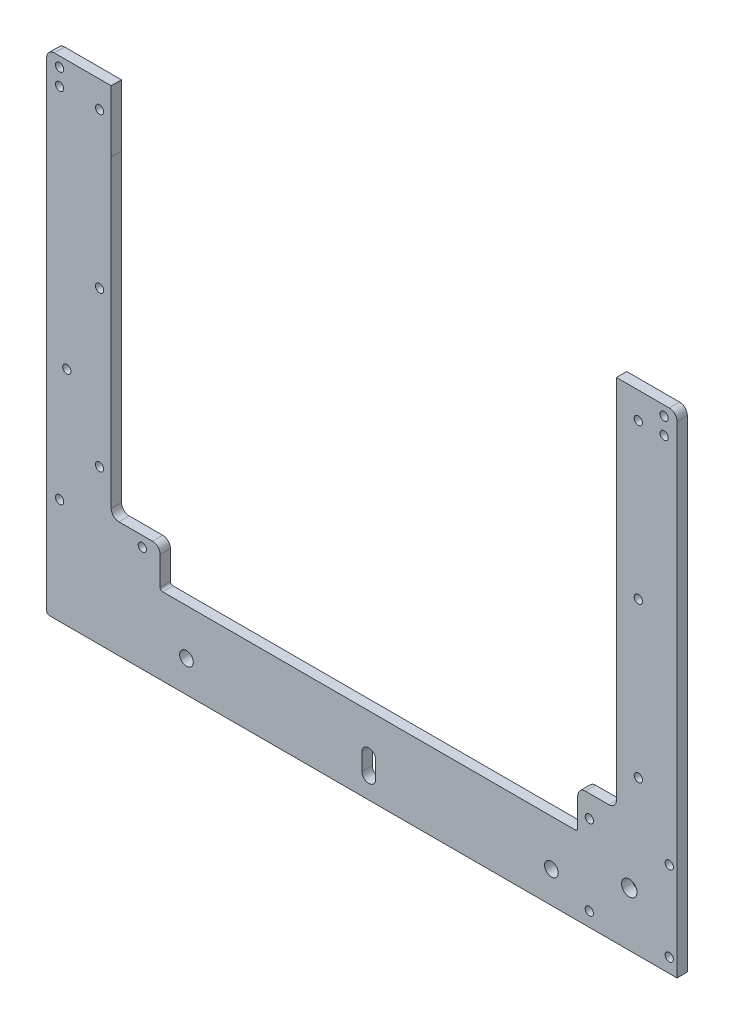
SolidWorks part; units mm, degrees
ref_plane "Plano frontal" through (0, 0, 0) normal (0, 0, 1) x (1, 0, 0)
ref_plane "Plano superior" through (0, 0, 0) normal (0, 1, 0) x (1, 0, 0)
ref_plane "Plano direito" through (0, 0, 0) normal (1, 0, 0) x (0, 0, -1)
sketch "Esboço1" plane through (0, 0, 0) normal (0, 0, 1) x (1, 0, 0)
  line L0 (-36.7564, -93.1156) -> (-55.7564, -93.1156)
  line L1 (-35.7564, -108.1156) -> (124.2436, -108.1156)
  line L2 (-55.7564, -79.1156) -> (-55.7564, 27.8844)
  line L3 (-52.7564, 30.8844) -> (141.2436, 30.8844)
  line L4 (144.2436, -79.1156) -> (144.2436, 27.8844)
  line L5 (168.2436, -138.1156) -> (-79.7564, -138.1156)
  line L6 (169.2436, -137.1156) -> (169.2436, 48.8844)
  line L7 (166.2436, 51.8844) -> (-77.7564, 51.8844)
  line L8 (-80.7564, -137.1156) -> (-80.7564, 48.8844)
  line L9 (44.2436, -142.1156) -> (44.2436, -132.526) construction
  line L10 (144.2436, -93.1156) -> (144.2436, -79.1156)
  line L11 (-36.7564, -93.1156) -> (-36.7564, -107.1156)
  line L12 (125.2436, -93.1156) -> (144.2436, -93.1156)
  line L13 (-36.7564, -93.1156) -> (-41.6564, -93.1156) construction
  line L15 (125.2436, -93.1156) -> (125.2436, -107.1156)
  line L17 (-55.7564, -93.1156) -> (-55.7564, -79.1156)
  arc A2 (141.2436, 30.8844) -> (144.2436, 27.8844) centre (141.2436, 27.8844) cw
  arc A3 (-55.7564, 27.8844) -> (-52.7564, 30.8844) centre (-52.7564, 27.8844) cw
  arc A4 (-77.7564, 51.8844) -> (-80.7564, 48.8844) centre (-77.7564, 48.8844) ccw
  arc A5 (169.2436, 48.8844) -> (166.2436, 51.8844) centre (166.2436, 48.8844) ccw
  arc A6 (-36.7564, -107.1156) -> (-35.7564, -108.1156) centre (-35.7564, -107.1156) ccw
  arc A7 (-79.7564, -138.1156) -> (-80.7564, -137.1156) centre (-79.7564, -137.1156) cw
  arc A9 (168.2436, -138.1156) -> (169.2436, -137.1156) centre (168.2436, -137.1156) ccw
  arc A12 (125.2436, -107.1156) -> (124.2436, -108.1156) centre (124.2436, -107.1156) cw
  dimension "D2" = 1
  dimension "D10" = 44
  dimension "D11" = 3
  dimension "D12" = 45
  dimension "D13" = 1
  dimension "D3" = 250
  dimension "D4" = 190
  dimension "D5" = 21
  dimension "D6" = 30
  dimension "D7" = 25
  dimension "D8" = 25
  dimension "D9" = 45
extrude "Ressalto-extrusão1" add sketch "Esboço1" along normal blind 4
fillet "Filete1" radius 3 4 edges at (144.2436, -93.1156, 2) (125.2436, -93.1156, 2) (-55.7564, -93.1156, 2) (-36.7564, -93.1156, 2)
hole_wizard "M3 Clearance Hole1" positions "Esboço11" profile "Esboço10" hole size "M3" standard "ISO" end condition through all
sketch "Esboço11" plane through (0, 0, 0) normal (0, 0, -1) x (-1, 0, 0)
  point P0 (-164.23, -97.103)
  point P12 (43.67, -97.103)
  point P15 (75.7428, -97.103)
sketch "Esboço10" plane through (164.23, -97.103, 0) normal (1, 0, 0) x (0, 1, 0)
  line L0 (0, 0) -> (0, 4)
  line L1 (0, 4) -> (1.6, 4)
  line L2 (1.6, 4) -> (1.6, 0)
  line L5 (1.6, 0) -> (0, 0)
  line L11 (0, -6.35) -> (0, 107.95) construction
  dimension "Thru Hole Dia." = 3.2
  dimension "Thru Hole Depth" = 4
sketch "Esboço16" plane through (0, 0, 4) normal (0, 0, 1) x (1, 0, 0)
  line L0 (150.0557, -138.1156) -> (169.2436, -138.1156) construction
  line L3 (-79.7564, -138.1156) -> (168.2436, -138.1156) construction
  line L5 (169.2436, -137.1156) -> (169.2436, 48.8844) construction
  line L6 (169.2436, -127.14) -> (169.2436, -138.1156) construction
hole_wizard "Furo com folga de M32" positions "Esboço19" profile "Esboço18" hole size "M3" standard "Ansi Metric" end condition through all
sketch "Esboço19" plane through (0, 0, 4) normal (0, 0, 1) x (1, 0, 0)
  point P14 (44.2436, 46.9871)
sketch "Esboço18" plane through (44.2436, 46.9871, 4) normal (1, 0, 0) x (0, -1, 0)
  line L0 (0, 0) -> (0, 4)
  line L1 (0, 4) -> (1.435, 4)
  line L2 (1.435, 4) -> (1.435, 0)
  line L5 (1.435, 0) -> (0, 0)
  line L11 (0, -6.35) -> (0, 107.95) construction
  dimension "Thru Hole Dia." = 2.87
  dimension "Thru Hole Depth" = 4
hole_wizard "M3 Clearance Hole2" positions "Sketch2" profile "Sketch1" hole size "M3" standard "ISO" end condition through all
sketch "Sketch2" plane through (0, 0, 4) normal (0, 0, 1) x (1, 0, 0)
  point P0 (161.5603, 35.4802)
  point P3 (161.5603, 4.4802)
sketch "Sketch1" plane through (161.5603, 35.4802, 4) normal (1, 0, 0) x (0, -1, 0)
  line L0 (0, 0) -> (0, 4)
  line L1 (0, 4) -> (1.6, 4)
  line L2 (1.6, 4) -> (1.6, 0)
  line L5 (1.6, 0) -> (0, 0)
  line L11 (0, -6.35) -> (0, 107.95) construction
  dimension "Thru Hole Dia." = 3.2
  dimension "Thru Hole Depth" = 4
sketch "Sketch3" plane through (0, 0, 4) normal (0, 0, 1) x (1, 0, 0)
  line L3 (44.2436, 30.8844) -> (44.2436, 18.6097) construction
  line L8 (141.2436, 30.8844) -> (-52.7564, 30.8844) construction
  line L9 (183.6742, -138.1156) -> (156.2436, -138.1156)
  line L10 (183.6742, 51.8844) -> (183.6742, -138.1156)
  line L11 (156.2436, 51.8844) -> (183.6742, 51.8844)
  line L12 (156.2436, -138.1156) -> (156.2436, 51.8844)
extrude "Cut-Extrude1" cut sketch "Sketch3" against normal blind 10
sketch "Sketch5" plane through (0, 0, 0) normal (0, 0, -1) x (-1, 0, 0)
  line L0 (-44.2436, 30.8844) -> (-44.2436, 20.8984) construction
  line L1 (-141.2436, 30.8844) -> (52.7564, 30.8844) construction
  line L2 (-145.2403, -97.5002) -> (-140.2436, -97.5002)
  line L3 (-145.2403, 30.8844) -> (-145.2403, -97.5002)
  line L4 (-141.2436, 30.8844) -> (52.7564, 30.8844) construction
  line L6 (-137.2442, 30.8844) -> (-145.2403, 30.8844)
  line L10 (-140.2436, 27.9415) -> (-140.2436, -97.5002)
  arc A0 (-137.2442, 30.8844) -> (-140.2436, 27.9415) centre (-137.2442, 27.8844) ccw
  dimension "D1" = 3
extrude "Boss-Extrude1" add sketch "Sketch5" against normal blind 4
fillet "Fillet3" radius 3 1 edges at (156.2436, 51.8844, 2)
sketch "Sketch10" plane through (0, 0, 0) normal (0, 0, -1) x (-1, 0, 0)
  line L0 (-156.2436, -138.1156) -> (-156.2436, 48.8844)
  line L1 (-156.2436, -138.1156) -> (-163.7436, -138.1156)
  line L4 (-150.0557, -138.1156) -> (-169.2436, -138.1156) construction
  line L6 (-163.7436, -138.1156) -> (-163.7436, 51.8844)
  line L10 (-163.7436, 51.8844) -> (-153.2436, 51.8844)
  arc A1 (-153.2436, 51.8844) -> (-156.2436, 48.8844) centre (-153.2436, 48.8844) ccw
extrude "Boss-Extrude3" add sketch "Sketch10" against normal blind 4
hole_wizard "M3 Clearance Hole4" positions "Sketch12" profile "Sketch11" hole size "M3" standard "ISO" end condition through all
sketch "Sketch12" plane through (0, 0, 0) normal (0, 0, -1) x (-1, 0, 0)
  point P0 (-160.7436, -101.6156)
  point P2 (-160.7436, -132.6156)
  point P5 (-129.7436, -132.6156)
  point P6 (-129.7436, -101.6156)
sketch "Sketch11" plane through (160.7436, -101.6156, 0) normal (1, 0, 0) x (0, 1, 0)
  line L0 (0, 0) -> (0, 4)
  line L1 (0, 4) -> (1.6, 4)
  line L2 (1.6, 4) -> (1.6, 0)
  line L5 (1.6, 0) -> (0, 0)
  line L11 (0, -6.35) -> (0, 107.95) construction
  dimension "Thru Hole Dia." = 3.2
  dimension "Thru Hole Depth" = 4
fillet "Fillet5" radius 3 2 edges at (163.7436, 51.8844, 2) (140.2436, -93.1156, 2)
hole_wizard "M5 Clearance Hole1" positions "Esboço15" profile "Esboço14" hole size "M5" standard "ISO" end condition through all
sketch "Esboço15" plane through (0, 0, 0) normal (0, 0, -1) x (-1, 0, 0)
  point P1 (-115.0336, -125.8856)
  point P3 (26.5464, -125.8856)
  point P4 (-44.1899, -129.8656)
sketch "Esboço14" plane through (115.0336, -125.8856, 0) normal (1, 0, 0) x (0, 1, 0)
  line L0 (0, 0) -> (0, 4)
  line L1 (0, 4) -> (2.65, 4)
  line L2 (2.65, 4) -> (2.65, 0)
  line L5 (2.65, 0) -> (0, 0)
  line L11 (0, -6.35) -> (0, 107.95) construction
  dimension "Thru Hole Dia." = 5.3
  dimension "Thru Hole Depth" = 4
sketch "Sketch15" plane through (0, 0, 0) normal (0, 0, -1) x (-1, 0, 0)
  circle A1 centre (-145.2436, -117.1156) radius 3
  point P0 (-145.2436, -117.1156)
  point P2 (-144.7712, -129.7569)
  point P4 (-145.2436, -117.1156)
  point P5 (-144.7712, -129.7569)
  dimension "D1" = 6
extrude "Cut-Extrude6" cut sketch "Sketch15" against normal through all
sketch "Sketch17" plane through (0, 0, 0) normal (0, 0, -1) x (-1, 0, 0)
  line L1 (-140.2436, 27.9415) -> (55.7564, 27.9415)
  line L2 (-140.2436, 27.9415) -> (-140.2436, 51.8844)
  line L3 (-140.2436, 51.8844) -> (55.7564, 51.8844)
  line L4 (55.7564, 27.9415) -> (55.7564, 51.8844)
extrude "Cut-Extrude8" cut sketch "Sketch17" against normal blind 5
sketch "Sketch23" plane through (0, 0, 4) normal (0, 0, 1) x (1, 0, 0)
  line L0 (-55.7564, 27.8844) -> (-55.7564, -90.1156) construction
  line L1 (-55.7564, -56.9456) -> (-19.6598, -56.9456)
  line L2 (-55.7564, -56.9456) -> (-55.7564, -46.9456)
  line L3 (-55.7564, -46.9456) -> (-19.6598, -46.9456)
  line L5 (-18.4098, -51.9456) -> (-16.0426, -51.9456) construction
  line L6 (-19.6598, 45.5544) -> (-55.7564, 45.5544)
  line L8 (-19.6598, 35.5544) -> (-55.7564, 35.5544)
  line L9 (-55.7564, 45.5544) -> (-55.7564, 35.5544)
  arc A1 (-19.6598, -50.6956) -> (-19.6598, -53.1956) centre (-19.6598, -51.9456) ccw construction
  arc A2 (-19.6598, 35.5544) -> (-19.6598, 45.5544) centre (-19.6598, 40.5544) ccw
  arc A3 (-19.6598, -56.9456) -> (-19.6598, -46.9456) centre (-19.6598, -51.9456) ccw
  dimension "D1" = 10
  dimension "10" = 10
extrude "Boss-Extrude4" [suppressed] add sketch "Sketch23" against normal up to surface (4 mm away) up to face at (142.2436, -117.1156, 0)
hole_wizard "M3 Clearance Hole6" positions "Esboço3" profile "Esboço2" hole size "M3" standard "ISO" end condition through all
sketch "Esboço3" plane through (0, 0, 0) normal (0, 0, -1) x (-1, 0, 0)
  line L2 (-148.7436, -78.3479) -> (-148.7436, -20.0979) construction
  line L3 (-148.7436, -20.0979) -> (-148.7436, 41.6521) construction
  point P0 (-148.7436, -78.3479)
  point P3 (-148.7436, -18.3479)
  point P6 (-148.7436, 41.6521)
  point P15 (60.2564, 41.6521)
  point P16 (60.2564, -18.3479)
  point P17 (60.2564, -78.3479)
  point P32 (72.9598, -51.9456)
sketch "Esboço2" plane through (148.7436, -78.3479, 0) normal (1, 0, 0) x (0, 1, 0)
  line L0 (0, 0) -> (0, 4)
  line L1 (0, 4) -> (1.6, 4)
  line L2 (1.6, 4) -> (1.6, 0)
  line L5 (1.6, 0) -> (0, 0)
  line L11 (0, -6.35) -> (0, 107.95) construction
  dimension "Thru Hole Dia." = 3.2
  dimension "Thru Hole Depth" = 4
hole_wizard "M3 Clearance Hole5" positions "Sketch21" profile "Sketch18" hole size "M3" standard "ISO" end condition through all
sketch "Sketch21" plane through (0, 0, 4) normal (0, 0, 1) x (1, 0, 0)
  line L0 (-80.7564, 48.8844) -> (-80.7564, -137.1156) construction
  line L1 (163.7436, 48.8844) -> (163.7436, -138.1156) construction
  line L2 (-60.2564, 41.6521) -> (158.7436, 41.6521) construction
  point P0 (-75.7564, 41.6521)
  point P2 (-75.7564, 48.1521)
  point P4 (158.7436, 48.1521)
  point P6 (158.7436, 41.6521)
  dimension "D1" = 5
  dimension "D2" = 5
  dimension "D3" = 6.5
  dimension "D4" = 5
  dimension "D5" = 5
  dimension "D6" = 6.5
sketch "Sketch18" plane through (-75.7564, 41.6521, 4) normal (1, 0, 0) x (0, -1, 0)
  line L0 (0, 0) -> (0, 4)
  line L1 (0, 4) -> (1.6, 4)
  line L2 (1.6, 4) -> (1.6, 0)
  line L5 (1.6, 0) -> (0, 0)
  line L11 (0, -6.35) -> (0, 107.95) construction
  dimension "Thru Hole Dia." = 3.2
  dimension "Thru Hole Depth" = 4
sketch "Sketch22" plane through (0, 0, 0) normal (0, 0, -1) x (-1, 0, 0)
  line L0 (-44.1899, -129.8656) -> (-44.1899, -123.2156) construction
  line L2 (-46.8408, -129.8656) -> (-46.8408, -123.2156)
  line L3 (-41.539, -129.8656) -> (-41.539, -123.2156)
  arc A0 (-46.8408, -129.8656) -> (-41.539, -129.8656) centre (-44.1899, -129.8656) ccw
  arc A1 (-41.539, -123.2156) -> (-46.8408, -123.2156) centre (-44.1899, -123.2156) ccw
  point P5 (-44.1899, -126.5406)
extrude "Cut-Extrude9" cut sketch "Sketch22" against normal blind 4
fillet "Fillet6" [suppressed] radius 10
